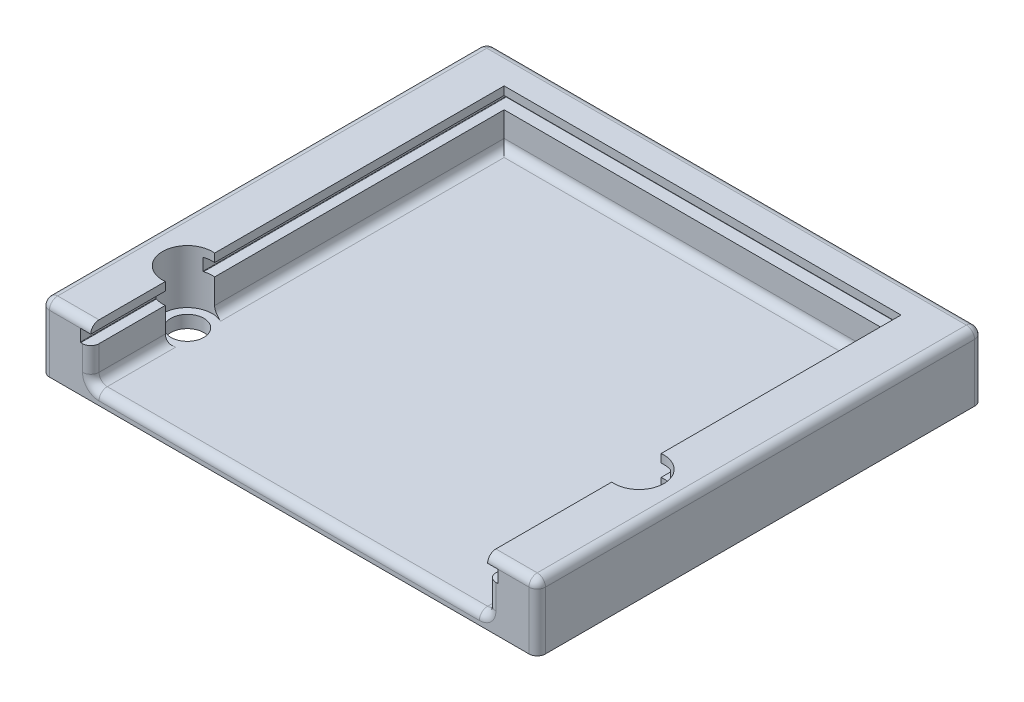
SolidWorks part; units mm, degrees
note: The reader was unsure of these and kept them because the rebuilt part matched: shared geometry of "Sketch2<7>".
ref_plane "Front Plane" through (0, 0, 0) normal (0, 0, 1) x (1, 0, 0)
ref_plane "Top Plane" through (0, 0, 0) normal (0, 1, 0) x (1, 0, 0)
ref_plane "Right Plane" through (0, 0, 0) normal (1, 0, 0) x (0, 0, -1)
sketch "Sketch2" plane through (0, 0, 0) normal (0, 1, 0) x (1, 0, 0)
  line L1 (0, 0) -> (60, 0)
  line L2 (0, 0) -> (0, 50)
  line L3 (0, 50) -> (60, 50)
  line L4 (60, 0) -> (60, 50)
  line L12 (6, 50) -> (6, 0)
  line L13 (54, 50) -> (54, 0)
  line L14 (0, 0) -> (-2, 0)
  line L15 (0, 25) -> (6, 25) construction
  line L16 (-2, 0) -> (-4, 0)
  line L17 (54, 25) -> (60, 25) construction
  line L18 (60, 0) -> (59, 0)
  line L19 (59, 0) -> (61, 0)
  line L20 (0, 50) -> (0, 53.897)
  line L21 (0, 53.897) -> (60, 53.897)
  line L22 (60, 50) -> (60, 53.897)
  line L23 (54.3156, 18) -> (60, 18) construction
  line L24 (5.6844, 12) -> (0, 12) construction
  circle A0 centre (5.6844, 12) radius 2
  circle A1 centre (54.3156, 18) radius 2
  circle A2 centre (5.6844, 12) radius 3
  circle A3 centre (54.3156, 18) radius 3
  dimension "D3" = 12
  dimension "D8" = 1
  dimension "D1" = 48
  dimension "D2" = 50
  dimension "D4" = 18
  dimension "D5" = 49
  dimension "D7" = 1
  dimension "D9" = 60
extrude "Boss-Extrude1" add sketch "Sketch2" along normal blind 1.5 contours A3 L13 L3 L12 A2 L1 | L13 A3 A1 | L13 A3 A1 | L12 A2 A0 | L12 A2 A0
extrude "Boss-Extrude4" add sketch "Sketch2<7>" along normal blind 8 contours A0 L12 L3 L2 L1 | L3 L22 L21 L20 | A3 L13 L1 L4 L3
sketch "Sketch2<7>" plane through (0, 0, 0) normal (0, 1, 0) x (1, 0, 0) same geometry as "Sketch2"
sketch "Sketch3" plane through (0, 8, 0) normal (0, 1, 0) x (1, 0, 0)
  line L0 (5, 0) -> (5, 51)
  line L1 (54, 35.4917) -> (55, 35.4917) construction
  line L2 (0, 0) -> (6, 0) construction
  line L3 (5, 51) -> (55, 51)
  line L4 (55, 51) -> (55, 0)
  line L5 (54, 0) -> (60, 0) construction
  line L6 (5, 25.5) -> (6, 25.5) construction
  line L7 (6, 50) -> (6, 14.9833) construction
  line L8 (54, 50) -> (54, 20.9833) construction
  line L10 (30, 51) -> (30, 50) construction
  line L11 (6, 50) -> (54, 50) construction
  dimension "D1" = 50
sketch "Sketch6" plane through (6, 0, 0) normal (1, 0, 0) x (0, 0, -1)
  line L0 (0, 5.5) -> (50, 5.5)
  line L1 (0, 8) -> (0, 1.5) construction
  line L2 (50, 8) -> (50, 1.5) construction
  line L3 (0, 7) -> (50, 7)
  line L4 (0, 7) -> (0, 5.5)
  line L5 (50, 7) -> (50, 5.5)
  line L8 (9.0167, 1.5) -> (0, 1.5) construction
  dimension "D1" = 1.5
  dimension "D2" = 4
extrude "Cut-Extrude1" cut sketch "Sketch6" against normal blind 1.25
sketch "Sketch10" plane through (54, 0, 0) normal (-1, 0, 0) x (0, 0, 1)
  line L0 (-50, 8) -> (-50, 1.5) construction
  line L1 (-50, 5.5) -> (0, 5.5)
  line L2 (-50, 5.5) -> (-50, 7)
  line L3 (-50, 7) -> (0, 7)
  line L4 (0, 5.5) -> (0, 7)
  line L5 (0, 8) -> (0, 1.5) construction
  line L7 (-15.0167, 1.5) -> (0, 1.5) construction
  dimension "D1" = 1.5
  dimension "D2" = 4
extrude "Cut-Extrude2" cut sketch "Sketch10" against normal blind 1.25
sketch "Sketch11" plane through (0, 0, -50) normal (0, 0, 1) x (1, 0, 0)
  line L1 (4.75, 5.5) -> (55.25, 5.5)
  line L2 (4.75, 5.5) -> (4.75, 7)
  line L3 (4.75, 7) -> (55.25, 7)
  line L4 (55.25, 5.5) -> (55.25, 7)
extrude "Cut-Extrude3" cut sketch "Sketch11" against normal blind 1.5
fillet "Fillet1" radius 1 17 edges at (6, 1.5, -4.5083) (6, 1.5, -32.4917) (30, 1.5, -50) (54, 1.5, -35.4917) (54, 1.5, -7.5083) (30, 1.5, 0) (54, 3.5, 0) (6, 3.5, 0) (60, 4, -53.897) (0, 4, -53.897) (30, 8, -53.897) (0, 4, 0) (60, 4, 0) (60, 8, -26.9485) (57, 8, 0) (3, 8, 0) (0, 8, -26.9485)
fillet "Fillet2" radius 0.05 6 edges at (4.75, 7, -4.5746) (4.75, 5.5, -4.5746) (30, 7, -51.5) (30, 5.5, -51.5) (55.25, 5.5, -7.5746) (55.25, 7, -7.5746)
